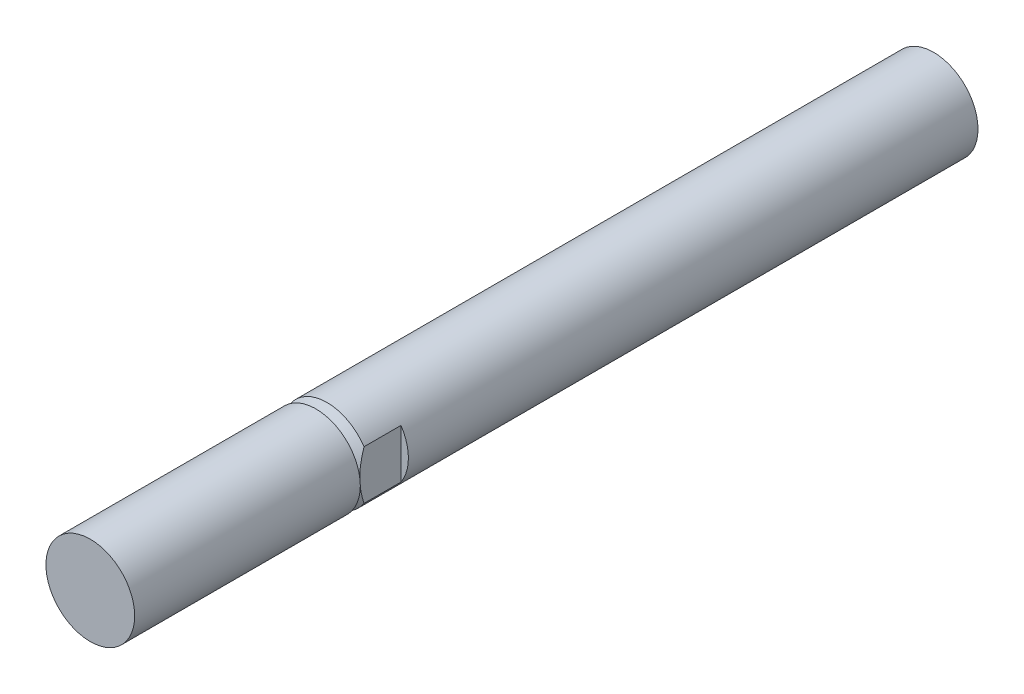
SolidWorks part; units mm, degrees
ref_plane "Front" through (0, 0, 0) normal (0, 0, 1) x (1, 0, 0)
ref_plane "Top" through (0, 0, 0) normal (0, 1, 0) x (1, 0, 0)
ref_plane "Right" through (0, 0, 0) normal (1, 0, 0) x (0, 0, -1)
sketch "support-front" plane through (0, 0, 0) normal (0, 0, 1) x (1, 0, 0)
  circle A1 centre (0, 0) radius 3
  dimension "diam-rod" = 6
sketch "support-right" plane through (0, 0, 0) normal (1, 0, 0) x (0, 0, -1)
  line L1 (0, 3) -> (57, 3)
  line L2 (0, 3) -> (0, -3)
  line L3 (0, -3) -> (57, -3)
  line L4 (57, 3) -> (57, -3)
  line L5 (0, 0) -> (57, 0) construction
  line L6 (10, 3) -> (10, -3) construction
  dimension "length-constant" = 47
  dimension "stroke" = 10
  dimension "length" = 57
sketch "support-right-thread" plane through (0, 0, 0) normal (1, 0, 0) x (0, 0, -1)
  line L0 (0, 3) -> (15.25, 3)
  line L1 (15.25, 3) -> (15.625, 2.3505)
  line L2 (15.625, 2.3505) -> (16, 3)
  line L3 (16, 3) -> (16, 5.8212)
  line L4 (16, 5.8212) -> (0, 5.8212)
  line L5 (0, 5.8212) -> (0, 3)
  line L6 (15.25, 3) -> (16, 3) construction
  line L7 (15.625, 2.3505) -> (15.625, 3) construction
  line L8 (0, 0) -> (57, 0) construction
  line L9 (0, 0) -> (57, 0) construction
  line L10 (0, 3) -> (0, -3) construction
  line L11 (16, 5.8212) -> (0, 3) construction
  line L12 (0, 3) -> (57, 3) construction
  line L13 (16, 3) -> (15.625, 2.4644) construction
  circle A0 centre (15.625, 2.4644) radius 0.057
  dimension "D1" = 60
  dimension "pitch" = 0.75
  dimension "diam-thread" = 6
  dimension "length-thread" = 16
  dimension "D3" = 10
  dimension "D4" = 5
sketch "support-top-key" plane through (0, 0, 0) normal (0, 1, 0) x (1, 0, 0)
  line L0 (0, 0) -> (0, 57) construction
  line L1 (-5.375, 15.625) -> (-2.5, 15.625)
  line L2 (-5.375, 15.625) -> (-5.375, 18.5)
  line L3 (-5.375, 18.5) -> (-2.5, 18.5)
  line L4 (-2.5, 15.625) -> (-2.5, 18.5)
  line L5 (5.375, 15.625) -> (2.5, 15.625)
  line L6 (5.375, 15.625) -> (5.375, 18.5)
  line L7 (5.375, 18.5) -> (2.5, 18.5)
  line L8 (2.5, 15.625) -> (2.5, 18.5)
  line L9 (0, 0) -> (0, 57) construction
  line L10 (0, 15.25) -> (0, 16) construction
  line L11 (-5.375, 16) -> (5.375, 16) construction
  line L12 (-4.5799, 15.625) -> (0, 15.625) construction
  point P10 (0, 15.25)
  point P11 (0, 15.625)
  point P12 (0, 16)
  dimension "width-key" = 5
  dimension "length-key" = 2.5
ref_plane "ref-plane-front" through (0, 0, 0) normal (0, 0, 1) x (1, 0, 0)
ref_plane "ref-plane-end" through (0, 0, -57) normal (0, 0, 1) x (1, 0, 0)
ref_axis "ref-axis-center" through (0, 0, -57) along (0, 0, 1)
ref_plane "ref-plane-thread" through (0, 0, -16) normal (0, 0, 1) x (1, 0, 0)
sketch "Sketch3" plane through (0, 0, 0) normal (0, 0, 1) x (1, 0, 0)
  circle A1 centre (0, 0) radius 3 construction
  circle A2 centre (0, 0) radius 3
extrude "body" add sketch "Sketch3" against normal up to surface (57 mm away) up to plane "ref-plane-end"
sketch "Sketch5" plane through (0, 0, 0) normal (1, 0, 0) x (0, 0, -1)
  line L0 (0, 0) -> (57, 0) construction
  line L1 (0, 0) -> (57, 0) construction
  line L6 (15.625, 2.3505) -> (16, 3)
  line L7 (15.25, 3) -> (15.625, 2.3505)
  line L8 (0, 3) -> (15.25, 3)
  line L9 (0, 5.8212) -> (0, 3)
  line L10 (16, 5.8212) -> (0, 5.8212)
  line L11 (16, 3) -> (16, 5.8212)
  line L12 (15.625, 2.3505) -> (16, 3)
  line L13 (15.25, 3) -> (15.625, 2.3505)
  line L14 (0, 3) -> (15.25, 3)
  line L15 (0, 5.8212) -> (0, 3)
  line L16 (16, 5.8212) -> (0, 5.8212)
  line L17 (16, 3) -> (16, 5.8212)
  dimension "D1" = 0
revolve "cut-thread" cut sketch "Sketch5" angle 360 about L1
sketch "Sketch7" plane through (0, 0, 0) normal (0, 1, 0) x (1, 0, 0)
  line L4 (2.5, 15.625) -> (5.375, 15.625)
  line L5 (2.5, 18.5) -> (2.5, 15.625)
  line L6 (5.375, 18.5) -> (2.5, 18.5)
  line L7 (5.375, 15.625) -> (5.375, 18.5)
  line L8 (2.5, 15.625) -> (5.375, 15.625)
  line L9 (2.5, 18.5) -> (2.5, 15.625)
  line L10 (5.375, 18.5) -> (2.5, 18.5)
  line L11 (5.375, 15.625) -> (5.375, 18.5)
  line L12 (-5.375, 15.625) -> (-2.5, 15.625)
  line L13 (-2.5, 15.625) -> (-2.5, 18.5)
  line L14 (-2.5, 18.5) -> (-5.375, 18.5)
  line L15 (-5.375, 18.5) -> (-5.375, 15.625)
  line L16 (-5.375, 15.625) -> (-2.5, 15.625)
  line L17 (-2.5, 15.625) -> (-2.5, 18.5)
  line L18 (-2.5, 18.5) -> (-5.375, 18.5)
  line L19 (-5.375, 18.5) -> (-5.375, 15.625)
  dimension "D1" = 0
  dimension "D2" = 0
extrude "cut-key" cut sketch "Sketch7" against normal through all and the other way through all
